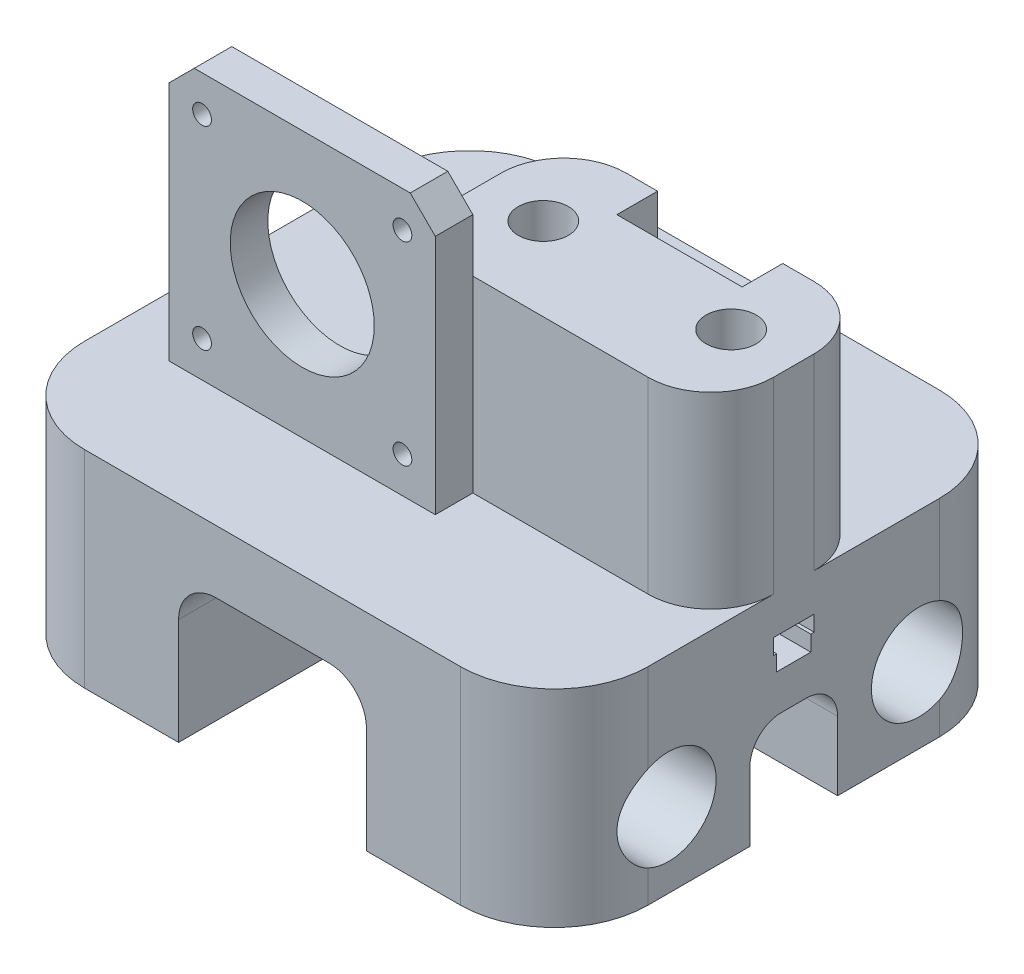
SolidWorks part; units mm, degrees
ref_plane "Front Plane" through (0, 0, 0) normal (0, 0, 1) x (1, 0, 0)
ref_plane "Top Plane" through (0, 0, 0) normal (0, 1, 0) x (1, 0, 0)
ref_plane "Right Plane" through (0, 0, 0) normal (1, 0, 0) x (0, 0, -1)
sketch "Sketch1" plane through (0, 0, 0) normal (0, 1, 0) x (1, 0, 0)
  line L0 (-45, 0) -> (45, 0) construction
  line L1 (-30, 38.25) -> (30, 38.25)
  line L2 (-45, 23.25) -> (-45, -23.25)
  line L3 (-30, -38.25) -> (30, -38.25)
  line L4 (45, 23.25) -> (45, -23.25)
  line L5 (-45, 38.25) -> (45, -38.25) construction
  line L6 (-45, -38.25) -> (45, 38.25) construction
  line L7 (0, 38.25) -> (0, -38.25) construction
  line L8 (-15, 38.25) -> (-15, 7)
  line L9 (15, 38.25) -> (15, 7)
  line L10 (-45, -7) -> (-15, -7)
  line L11 (-45, 7) -> (-15, 7)
  line L12 (15, 7) -> (45, 7)
  line L13 (-45, 7) -> (45, 7) construction
  line L14 (-15, -7) -> (-15, -38.25)
  line L15 (-15, 38.25) -> (-15, -38.25) construction
  line L16 (15, -7) -> (45, -7)
  line L17 (-45, -7) -> (45, -7) construction
  line L18 (15, -7) -> (15, -38.25)
  line L19 (15, 38.25) -> (15, -38.25) construction
  arc A0 (-45, -23.25) -> (-30, -38.25) centre (-30, -23.25) ccw
  arc A1 (30, -38.25) -> (45, -23.25) centre (30, -23.25) ccw
  arc A2 (30, 38.25) -> (45, 23.25) centre (30, 23.25) cw
  arc A3 (-30, 38.25) -> (-45, 23.25) centre (-30, 23.25) ccw
  point P1 (0, 0)
  dimension "D3" = 15
  dimension "D1" = 90
  dimension "D2" = 76.5
  dimension "D4" = 15
  dimension "D5" = 15
  dimension "D6" = 7
  dimension "D7" = 7
extrude "Boss-Extrude1" add sketch "Sketch1" along normal blind 33 contours L2 A0 L3 L14 L10 | L1 A3 L2 L11 L8 | L3 A1 L4 L16 L18 | A2 L1 L9 L12 L4 | L18 L16 L4 L12 L9 L1 L8 L11 L2 L10 L14 L3 region at (-29.3674, 0, -21.9585) region at (0, 0, 0) region at (29.3674, 0, -21.9585) region at (-29.3674, 0, 21.9585) region at (29.3674, 0, 21.9585)
sketch "Sketch2" plane through (0, 0, -38.25) normal (0, 0, -1) x (-1, 0, 0)
  line L0 (-15, 0) -> (-15, 17)
  line L1 (-9, 23) -> (9, 23)
  line L2 (15, 17) -> (15, 0)
  line L3 (-15, 0) -> (15, 0)
  arc A0 (9, 23) -> (15, 17) centre (9, 17) cw
  arc A1 (-15, 17) -> (-9, 23) centre (-9, 17) cw
  point P0 (15, 0)
  point P2 (-15, 0)
  point P12 (-15, 23)
  dimension "D2" = 6
  dimension "D1" = 23
extrude "Cut-Extrude1" cut sketch "Sketch2" against normal up to surface (76.5 mm away) up to face at (0, 16.5, 38.25)
sketch "Sketch3" plane through (45, 0, 0) normal (1, 0, 0) x (0, 0, -1)
  line L0 (-7, 0) -> (-7, 11)
  line L1 (-2, 16) -> (2, 16)
  line L2 (7, 11) -> (7, 0)
  arc A0 (2, 16) -> (7, 11) centre (2, 11) cw
  arc A1 (-7, 11) -> (-2, 16) centre (-2, 11) cw
  point P0 (7, 0)
  point P2 (-7, 0)
  point P12 (-7, 16)
  line M2 (-23.25, 0) -> (23.25, 0)
  dimension "D2" = 5
  dimension "D1" = 16
extrude "Cut-Extrude3" cut sketch "Sketch3" against normal blind 91 and the other way through all contours L2 L1 L0 M2 region at (45, 7.6537, 0)
sketch "Sketch5" plane through (45, 0, 0) normal (1, 0, 0) x (0, 0, -1)
  line L0 (0, 0) -> (0, 12) construction
  line L1 (-20, 12) -> (20, 12) construction
  circle A0 centre (-20, 12) radius 5
  circle A1 centre (20, 12) radius 5
  circle A2 centre (-20, 12) radius 7.6
  circle A3 centre (20, 12) radius 7.6
  line M5 (23.25, 0) -> (23.25, 33)
  line M7 (-23.25, 33) -> (-23.25, 0)
  dimension "D3" = 10
  dimension "D4" = 15.2
  dimension "D5" = 15.2
  dimension "D1" = 12
  dimension "D2" = 40
extrude "Cut-Extrude4" cut sketch "Sketch5" against normal blind 91 contours A0 M7 | A1 M5 | A1 M5 | A0 region at (45, 12, 19.4723) region at (45, 12, -23.9617) region at (45, 12, -19.4723)
extrude "Cut-Extrude5" cut sketch "Sketch5<3>" against normal blind 25 contours A2 A0 M7 | A2 A0 M7 | A3 A1 M5 | A3 A1 M5 region at (45, 16.7111, 17.8302) region at (45, 12, 25.3375) region at (45, 12, -25.3375) region at (45, 12, -14.8132)
sketch "Sketch5<3>" plane through (45, 0, 0) normal (1, 0, 0) x (0, 0, -1) same geometry as "Sketch5"
sketch "Sketch7" plane through (-45, 0, 0) normal (-1, 0, 0) x (0, 0, 1)
  circle A0 centre (20, 12) radius 7.6 construction
  circle A1 centre (-20, 12) radius 7.6 construction
  circle A2 centre (20, 12) radius 7.6
  circle A3 centre (-20, 12) radius 7.6
extrude "Cut-Extrude6" cut sketch "Sketch7" against normal blind 25
sketch "Sketch8" plane through (0, 33, 0) normal (0, 1, 0) x (1, 0, 0)
  line L5 (45, 0) -> (-5, 0) construction
  line L6 (45, 23.25) -> (45, -23.25) construction
  line L7 (5, 0) -> (35, 0) construction
  line L8 (-5, 13.25) -> (45, 13.25)
  line L9 (-5, 13.25) -> (-5, -13.25)
  line L10 (-5, -13.25) -> (45, -13.25)
  line L11 (45, 13.25) -> (45, -13.25)
  line L12 (-5, 13.25) -> (45, -13.25) construction
  line L13 (-5, -13.25) -> (45, 13.25) construction
  circle A2 centre (5, 0) radius 4
  circle A3 centre (35, 0) radius 4
  point P1 (20, 0)
  dimension "D4" = 30
  dimension "D3" = 8
  dimension "D1" = 50
  dimension "D2" = 26.5
extrude "Boss-Extrude2" add sketch "Sketch8" along normal blind 30 contours A2 region at (20, 33, 0)
sketch "Sketch12" plane through (0, 0, 13.25) normal (0, 0, 1) x (1, 0, 0)
  line L0 (-35.5, 33) -> (-35.5, 71.5)
  line L1 (-31.5, 75.5) -> (3, 75.5)
  line L2 (7, 71.5) -> (7, 33)
  line L3 (-30, 33) -> (30, 33) construction
  line L4 (7, 33) -> (-35.5, 33)
  line L5 (-35.5, 71.5) -> (-31.5, 75.5)
  line L6 (-30.25, 69.75) -> (1.75, 69.75) construction
  line L7 (-30.25, 69.75) -> (-30.25, 38.75) construction
  line L8 (-30.25, 38.75) -> (1.75, 38.75) construction
  line L9 (1.75, 69.75) -> (1.75, 38.75) construction
  line L10 (-30.25, 69.75) -> (1.75, 38.75) construction
  line L11 (-30.25, 38.75) -> (1.75, 69.75) construction
  line L12 (3, 75.5) -> (7, 71.5)
  line L13 (-5, 63) -> (-5, 33) construction
  line L14 (-14.25, 75.5) -> (-14.25, 33) construction
  circle A0 centre (-14.25, 54.25) radius 11.5
  circle A1 centre (-30.25, 69.75) radius 1.5
  circle A2 centre (1.75, 69.75) radius 1.5
  circle A3 centre (-30.25, 38.75) radius 1.5
  circle A4 centre (1.75, 38.75) radius 1.5
  point P1 (-35.5, 75.5)
  point P3 (7, 75.5)
  dimension "D5" = 3
  dimension "D6" = 23
  dimension "D1" = 31
  dimension "D2" = 32
  dimension "D3" = 42.5
  dimension "D4" = 42.5
  dimension "D7" = 12
extrude "Boss-Extrude5" add sketch "Sketch12" along normal blind 6
sketch "Sketch13" plane through (0, 0, -13.25) normal (0, 0, -1) x (-1, 0, 0)
  line L0 (-20, 63) -> (-20, 52.5) construction
  line L1 (5, 63) -> (-45, 63) construction
  line L2 (-19, 52.5) -> (-13, 52.5)
  line L3 (-10, 52.5) -> (-10, 63)
  line L4 (-21, 52.5) -> (-27, 52.5)
  line L5 (-30, 52.5) -> (-30, 63)
  line L6 (-29, 52.5) -> (-29, 47.5)
  line L7 (-29, 47.5) -> (-27, 47.5)
  line L8 (-27, 47.5) -> (-27, 52.5)
  line L9 (-19, 52.5) -> (-19, 47.5)
  line L10 (-19, 47.5) -> (-21, 47.5)
  line L11 (-21, 47.5) -> (-21, 52.5)
  line L12 (-11, 52.5) -> (-11, 47.5)
  line L13 (-11, 47.5) -> (-13, 47.5)
  line L14 (-13, 47.5) -> (-13, 52.5)
  line L15 (-30, 63) -> (-10, 63)
  line L16 (-20, 52.5) -> (-20, 55.7) construction
  line L17 (-20, 55.7) -> (-14, 55.7) construction
  line L18 (-29, 52.5) -> (-30, 52.5)
  line L19 (-11, 52.5) -> (-10, 52.5)
  circle A0 centre (-15.25, 55.7) radius 1.25 construction
  circle A1 centre (-15.25, 55.7) radius 1
  circle A2 centre (-24.75, 55.7) radius 1
  line M17 (5, 63) -> (-45, 63)
  dimension "D10" = 2.5
  dimension "D11" = 2
  dimension "D1" = 10.5
  dimension "D2" = 5
  dimension "D3" = 2
  dimension "D4" = 1
  dimension "D5" = 1
  dimension "D6" = 1
  dimension "D7" = 20
  dimension "D8" = 10
  dimension "D9" = 6
  dimension "D12" = 3.2
extrude "Cut-Extrude7" cut sketch "Sketch13" against normal blind 6.5 contours A2 | A1 | L12 L19 L3 L5 L18 L6 L7 L8 L4 L11 L10 L9 L2 L14 L13 A1 A2 M17 region at (20, 56.8103, -13.25) region at (15.25, 55.7, -13.25) region at (24.75, 55.7, -13.25)
extrude "Cut-Extrude8" cut sketch "Sketch13<3>" against normal blind 17 contours A1 | A2 region at (15.25, 55.7, -13.25)
sketch "Sketch13<3>" plane through (0, 0, -13.25) normal (0, 0, -1) x (-1, 0, 0) same geometry as "Sketch13"
ref_plane "Plane1" through (0, 22, 0) normal (0, -1, 0) x (-1, 0, 0)
sketch "Sketch15" plane through (0, 22, 0) normal (0, -1, 0) x (-1, 0, 0)
  line L0 (-45, 0) -> (-37, 0) construction
  line L1 (-38.5733, -2.725) -> (-50, -2.725)
  line L2 (-33.8534, 0) -> (-35.4267, 2.725)
  line L3 (-35.4267, 2.725) -> (-38.5733, 2.725)
  line L4 (-45, -2) -> (-15, -2)
  line L5 (-15, -2) -> (-15, 2)
  line L6 (-15, 2) -> (-45, 2)
  line L7 (-45, 2) -> (-45, -2)
  line L8 (-45, -2) -> (-15, -2) construction
  line L9 (-15, -2) -> (-15, 2)
  line L10 (-15, 2) -> (-45, 2) construction
  line L11 (-45, 2) -> (-45, -2)
  line L12 (-38.5733, 2.725) -> (-40.1466, 0) construction
  line L13 (-40.1466, 0) -> (-38.5733, -2.725) construction
  line L14 (-38.5733, -2.725) -> (-35.4267, -2.725)
  line L15 (-35.4267, -2.725) -> (-33.8534, 0)
  line L16 (-50, -2.725) -> (-50, 2.725)
  line L17 (-50, 2.725) -> (-38.5733, 2.725)
  line L18 (-30, 4.6402) -> (-30, -5.4041) construction
  line L19 (-10, -2.725) -> (-10, 2.725)
  line L20 (-10, 2.725) -> (-21.4267, 2.725)
  line L21 (-21.4267, -2.725) -> (-10, -2.725)
  line L22 (-19.8534, 0) -> (-21.4267, -2.725) construction
  line L23 (-21.4267, 2.725) -> (-19.8534, 0) construction
  line L24 (-24.5733, 2.725) -> (-21.4267, 2.725)
  line L25 (-26.1466, 0) -> (-24.5733, 2.725)
  line L26 (-24.5733, -2.725) -> (-26.1466, 0)
  line L27 (-21.4267, -2.725) -> (-24.5733, -2.725)
  line L28 (-45, 7) -> (-45, 2) construction
  circle A0 centre (-37, 0) radius 1.5
  circle A1 centre (-37, 0) radius 2.725 construction
  circle A2 centre (-23, 0) radius 1.5
  dimension "D3" = 3
  dimension "D2" = 5.45
  dimension "D4" = 8
  dimension "D5" = 5
  dimension "D1" = 0
extrude "Cut-Extrude9" cut sketch "Sketch15" against normal blind 2.5 contours L17 L3 L2 L15 L14 L1 L16 | L21 L19 L20 L24 L25 L26 L27
extrude "Cut-Extrude12" cut sketch "Sketch15<5>" along normal blind 9 contours A0 | A2 region at (37, 22, 0)
sketch "Sketch15<5>" plane through (0, 22, 0) normal (0, -1, 0) x (-1, 0, 0) same geometry as "Sketch15"
ref_plane "Plane2" through (0, 0, 0) normal (1, 0, 0) x (0, 0, -1)
sketch "Sketch16" plane through (45, 0, 0) normal (1, 0, 0) x (0, 0, -1)
  line L0 (-2.725, 24.5) -> (-3.25, 24.5)
  line L1 (-3.25, 24.5) -> (-3.25, 27)
  line L2 (-3.25, 27) -> (3.25, 27)
  line L3 (3.25, 27) -> (3.25, 24.5)
  line L4 (3.25, 24.5) -> (2.725, 24.5)
  line M5 (-2.725, 24.5) -> (2.725, 24.5)
  dimension "D1" = 6.5
  dimension "D2" = 2.5
extrude "Cut-Extrude13" cut sketch "Sketch16" against normal blind 35 and the other way through all contours L4 L3 L2 L1 L0 M5 region at (45, 25.75, 0)
mirror "Mirror1" about plane through (0, 0, 0) normal (1, 0, 0) of "Cut-Extrude9", "Cut-Extrude12", "Cut-Extrude13"
fillet "Fillet1" radius 10 3 edges at (-5, 48, -13.25) (45, 48, -13.25) (45, 48, 13.25)
ref_plane "Plane8" through (-12.32, 0, 0) normal (-1, 0, 0) x (0, 0, 1)
sketch "Sketch26" plane through (-12.32, 0, 0) normal (-1, 0, 0) x (0, 0, 1)
  line L0 (-3.25, 27) -> (-3.25, 24.5) construction
  line L1 (3.25, 27) -> (-3.25, 27) construction
  line L2 (3.25, 24.5) -> (3.25, 27) construction
  line L3 (-3.25, 27) -> (-3.25, 24.5)
  line L4 (3.25, 27) -> (-3.25, 27)
  line L5 (3.25, 24.5) -> (3.25, 27)
  line L6 (-2.725, 22) -> (2.725, 22) construction
  line L7 (2.725, 22) -> (0, 22) construction
  line L8 (-2.725, 22) -> (2.725, 22)
  line L9 (2.725, 22) -> (0, 22)
  line L10 (-3.25, 24.5) -> (-3.25, 22)
  line L11 (-3.25, 22) -> (-2.725, 22)
  line L12 (2.725, 22) -> (3.25, 22)
  line L13 (3.25, 22) -> (3.25, 24.5)
sketch3d "3DSketch4"
  line L0 (-10, 27, -3.25) -> (-12.32, 22, -3.25)
  line L1 (-12.32, 22, -3.25) -> (-12.32, 22, 3.25)
  line L2 (-12.32, 22, 3.25) -> (-10, 27, 3.25)
  line L3 (-10, 27, 3.25) -> (-10, 27, -3.25)
ref_plane "Plane9" through (-18.537, 8.6012, 0) normal (-0.9071, 0.4209, 0) x (0, 0, 1)
sketch "Sketch27" plane through (-18.537, 8.6012, 0) normal (-0.9071, 0.4209, 0) x (0, 0, 1)
  line L0 (-2.725, 14.7709) -> (2.725, 14.7709) construction
  line L1 (-3.25, 14.7709) -> (-2.725, 14.7709) construction
  line L2 (2.725, 14.7709) -> (3.25, 14.7709) construction
  line L3 (-3.25, 20.2829) -> (-3.25, 14.7709) construction
  line L4 (3.25, 14.7709) -> (3.25, 20.2829) construction
  line L5 (3.25, 20.2829) -> (-3.25, 20.2829) construction
  line L6 (-2.725, 14.7709) -> (2.725, 14.7709)
  line L7 (-3.25, 14.7709) -> (-2.725, 14.7709)
  line L8 (2.725, 14.7709) -> (3.25, 14.7709)
  line L9 (-3.25, 20.2829) -> (-3.25, 14.7709)
  line L10 (3.25, 14.7709) -> (3.25, 20.2829)
  line L11 (3.25, 20.2829) -> (-3.25, 20.2829)
revolve "Cut-Revolve3" cut sketch "Sketch27" angle 90 about L8 reverse direction yes
mirror "Mirror2" about plane through (0, 0, 0) normal (1, 0, 0) of "Cut-Revolve3"
extrude "Cut-Extrude14" cut sketch "Sketch26" against normal blind 2 contours L12 L13 L5 L4 L3 L10 L11 L8 region at (-12.32, 24.5, 0)
mirror "Mirror3" about plane through (0, 0, 0) normal (1, 0, 0) of "Cut-Extrude14"
sketch "Sketch29" plane through (0, 33, 0) normal (0, 1, 0) x (1, 0, 0)
  line L1 (7, 13.25) -> (9, 13.25) construction
  line L2 (5, 13.25) -> (10, 13.25) construction
  line L3 (9, 3.25) -> (9, 38.25) construction
  line L4 (9, 13.25) -> (7, 13.25) construction
  circle A0 centre (7, 15.25) radius 2
  dimension "D1" = 4
extrude "Cut-Extrude15" cut sketch "Sketch29" against normal blind 11
